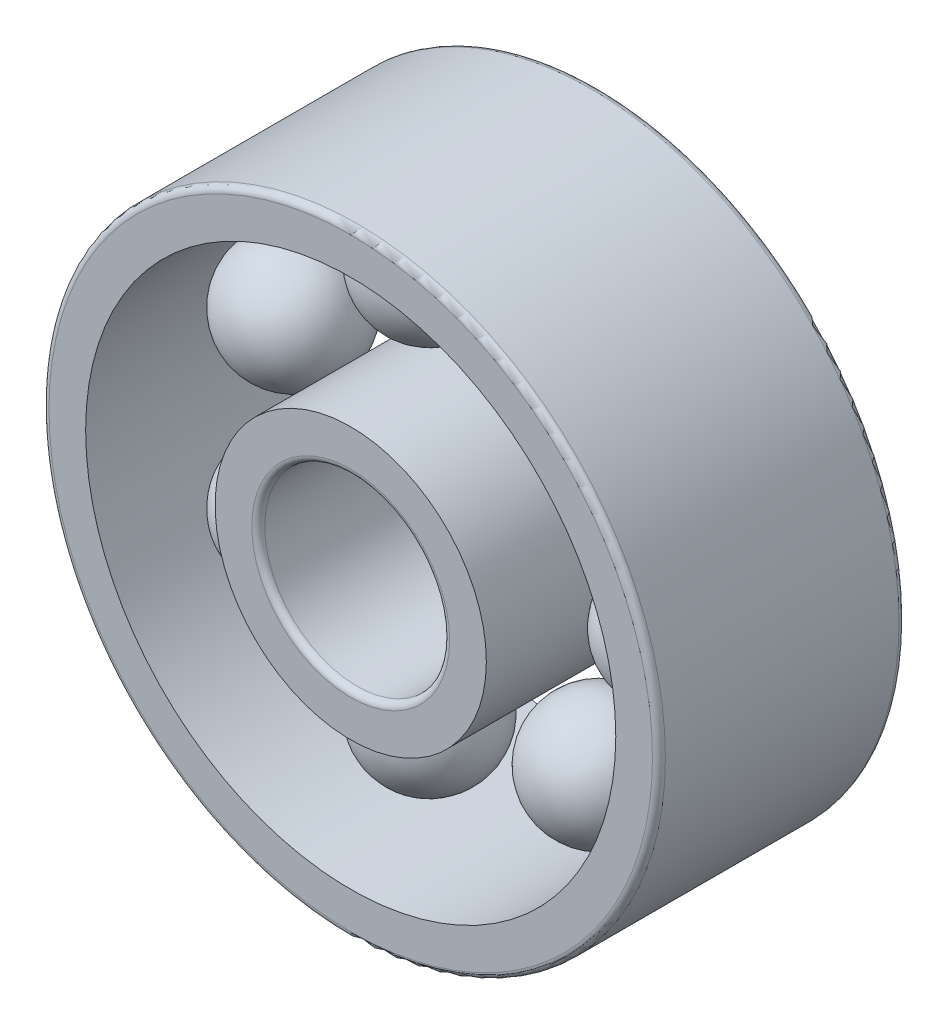
SolidWorks part; units mm, degrees
ref_plane "Front Plane" through (0, 0, 0) normal (0, 0, 1) x (1, 0, 0)
ref_plane "Top Plane" through (0, 0, 0) normal (0, 1, 0) x (1, 0, 0)
ref_plane "Right Plane" through (0, 0, 0) normal (1, 0, 0) x (0, 0, -1)
sketch "S" plane through (0, 0, 0) normal (0, 0, 1) x (1, 0, 0)
  line L0 (-2, 0) -> (2, 0) construction
  circle A0 centre (0, 0) radius 1.5 construction
  circle A1 centre (0, 0) radius 5 construction
  circle A2 centre (0, 0) radius 2.2 construction
  circle A3 centre (0, 0) radius 4.3 construction
  dimension "ID" = 3
  dimension "OD" = 10
  dimension "IDa" = 4.4
  dimension "ODa" = 8.6
  dimension "B" = 4
ref_axis "Z" through (0, 0, -2.2) along (0, 0, 1)
sketch "InnerS" plane through (0, 0, 0) normal (0, 1, 0) x (1, 0, 0)
  line L0 (1.5, -2) -> (2.2, -2)
  line L1 (2.2, -2) -> (2.2, 2)
  line L2 (2.2, 2) -> (1.5, 2)
  line L3 (1.5, 2) -> (1.5, -2)
  line L4 (0, -4) -> (0, 4) construction
  dimension "r1" = 1.5
  dimension "r2" = 2.2
  dimension "z1" = 2
  dimension "z2" = 2
revolve "InnerRing" add sketch "InnerS" angle 360 about L4
sketch "OuterS" plane through (0, 0, 0) normal (0, 1, 0) x (1, 0, 0)
  line L0 (4.3, -2) -> (5, -2)
  line L1 (5, -2) -> (5, 2)
  line L2 (5, 2) -> (4.3, 2)
  line L3 (4.3, 2) -> (4.3, -2)
  line L4 (0, -4) -> (0, 4) construction
  dimension "z1" = 2
  dimension "z2" = 2
  dimension "r1" = 4.3
  dimension "r2" = 5
revolve "OuterRing" add sketch "OuterS" angle 360 about L4
sketch "BallS" plane through (0, 0, 0) normal (0, 1, 0) x (1, 0, 0)
  line L0 (2.2525, 0) -> (4.2475, 0)
  arc A0 (2.2525, 0) -> (4.2475, 0) centre (3.25, 0) ccw
  dimension "r" = 0.9975
  dimension "p" = 3.25
revolve "Ball" add sketch "BallS" angle 360 about L0
pattern_circular "BallsPattern" count 7 over 360 about axis through (0, 0, -2.2) along (0, 0, 1) of bodies 103
fillet "F1" radius 0.105 2 edges at (5, 0, -2) (5, 0, 2)
fillet "F2" radius 0.105 2 edges at (1.5, 0, -2) (1.5, 0, 2)
equation "\"r1@InnerS\" = abs(0.5*\"ID@S\")"
equation "\"r2@InnerS\" = abs(0.5*\"IDa@S\")"
equation "\"z1@InnerS\" = abs(-0.5*\"B@S\")"
equation "\"z2@InnerS\" = abs(0.5*\"B@S\")"
equation "\"r1@OuterS\" = abs(0.5*\"ODa@S\")"
equation "\"r2@OuterS\" = abs(0.5*\"OD@S\")"
equation "\"z1@OuterS\" = abs(-0.5*\"B@S\")"
equation "\"z2@OuterS\" = abs(0.5*\"B@S\")"
equation "\"r@BallS\" = abs(0.2375*\"ODa@S\"-0.2375*\"IDa@S\")"
equation "\"p@BallS\" = abs(0.25*\"IDa@S\"+0.25*\"ODa@S\")"
equation "\"N@BallsPattern\" = int(2.417*(0.25*\"IDa@S\"+0.25*\"ODa@S\")/(0.2375*\"ODa@S\"-0.2375*\"IDa@S\"))"
equation "\"r_min@F2\" = \"r_min@F1\""
